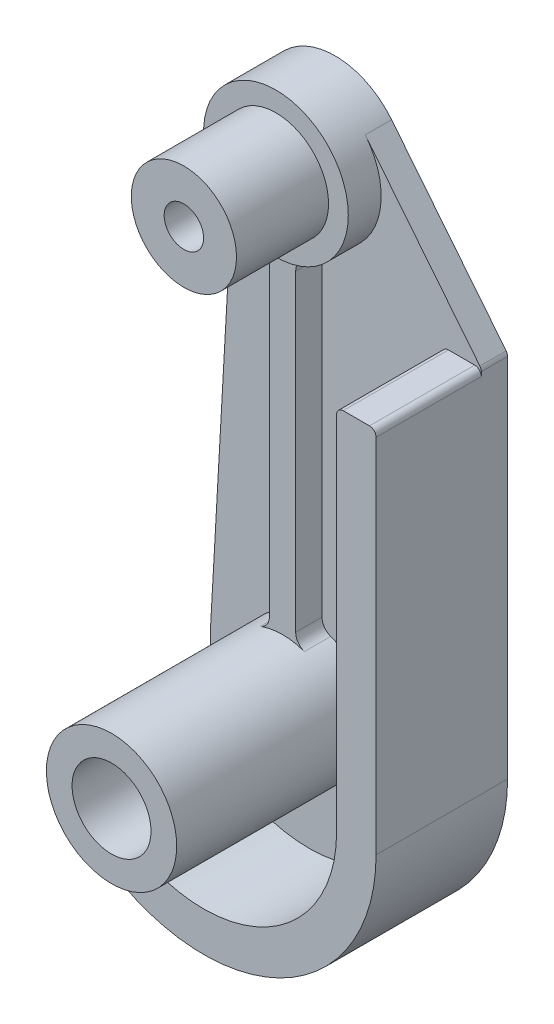
SolidWorks part; units mm, degrees
note: The reader was unsure of these and kept them because the rebuilt part matched: shared geometry of "Sketch1<3>", "Sketch1<5>", "Sketch1<6>", "Sketch1<7>".
ref_plane "Front Plane" through (0, 0, 0) normal (0, 0, 1) x (1, 0, 0)
ref_plane "Top Plane" through (0, 0, 0) normal (0, 1, 0) x (1, 0, 0)
ref_plane "Right Plane" through (0, 0, 0) normal (1, 0, 0) x (0, 0, -1)
sketch "Sketch1" plane through (0, 0, 0) normal (0, 0, 1) x (1, 0, 0)
  line L0 (0, 0) -> (0, 35.56) construction
  line L2 (13.1124, 0) -> (13.1124, 28)
  line L3 (0, 0) -> (0, 35.56) construction
  line L5 (10.1124, 0) -> (10.1124, 28)
  line L6 (10.1124, 0) -> (0, 0) construction
  line L7 (10.1124, 0) -> (13.1124, 0)
  line L8 (10.1124, 28) -> (13.1124, 28)
  line L9 (-7.4881, 0.4218) -> (-5.4913, 35.8693)
  line L10 (-5.0562, -8.7576) -> (-6.5562, -11.3556)
  line L11 (-5.0562, -8.7576) -> (0, 0) construction
  line L12 (-5.0562, -8.7576) -> (-3.75, -6.4952)
  line L13 (4.2908, 39.0008) -> (13.1124, 28)
  circle A0 centre (0, 0) radius 4.953
  circle A1 centre (0, 0) radius 3
  arc A2 (-6.5562, -11.3556) -> (13.1124, 0) centre (0, 0) ccw
  arc A4 (-5.0562, -8.7576) -> (10.1124, 0) centre (0, 0) ccw
  circle A6 centre (0, 35.56) radius 1.5
  circle A7 centre (0, 35.56) radius 5.5
  arc A8 (-7.4881, 0.4218) -> (-3.75, -6.4952) centre (0, 0) ccw
  circle A9 centre (0, 35.56) radius 4
  dimension "D1" = 6
  dimension "D2" = 9.906
  dimension "D5" = 20.2248
  dimension "D6" = 3
  dimension "D8" = 3
  dimension "D9" = 11
  dimension "D12" = 150
  dimension "D13" = 7.5
  dimension "D4" = 8
  dimension "D11" = 28
  dimension "D14" = 35.56
extrude "Boss-Extrude1" add sketch "Sketch1" along normal blind 2 contours A7 A6 | L9 A8 L12 A4 L5 L8 L13 A7 A0 | A0 A1 | L8 L5 L7 L2 | A4 L10 A2 L7
extrude "Boss-Extrude2" add sketch "Sketch1<3>" along normal blind 17 contours A0 A1
sketch "Sketch1<3>" plane through (0, 0, 0) normal (0, 0, 1) x (1, 0, 0) same geometry as "Sketch1"
extrude "Boss-Extrude3" add sketch "Sketch1<5>" along normal blind 10 contours L8 L5 L7 L2
sketch "Sketch1<5>" plane through (0, 0, 0) normal (0, 0, 1) x (1, 0, 0) same geometry as "Sketch1"
extrude "Boss-Extrude4" add sketch "Sketch1<6>" along normal blind 11.5 contours A9 A6
sketch "Sketch1<6>" plane through (0, 0, 0) normal (0, 0, 1) x (1, 0, 0) same geometry as "Sketch1"
extrude "Boss-Extrude5" add sketch "Sketch1<7>" along normal blind 2.5 from surface at 2 contours A7 A9 starting at face at (4, 35.56, 2)
sketch "Sketch1<7>" plane through (0, 0, 0) normal (0, 0, 1) x (1, 0, 0) same geometry as "Sketch1"
sketch "Sketch3" plane through (0, 0, 2) normal (0, 0, 1) x (1, 0, 0)
  line L1 (-1, 30.1517) -> (1, 30.1517)
  line L2 (-1, 30.1517) -> (-1, 4.851)
  line L3 (-1, 4.851) -> (1, 4.851)
  line L4 (1, 30.1517) -> (1, 4.851)
  circle A0 centre (0, 0) radius 4.953 construction
  circle A1 centre (0, 0) radius 4.953 construction
  arc A2 (-5.4913, 35.8693) -> (4.2908, 39.0008) centre (0, 35.56) ccw construction
  point P4 (1.1663, 4.8137)
  point P7 (-0.978, 4.8555)
  point P10 (-1, 30.1517)
  dimension "D1" = 2
extrude "Boss-Extrude6" add sketch "Sketch3" along normal blind 2
fillet "Fillet3" radius 0.5 2 edges at (13.1124, 28, 6) (10.1124, 28, 6)
fillet "Fillet4" radius 0.5 1 edges at (13.1124, 28, 1)
fillet "Fillet5" radius 0.5 3 edges at (-6.5562, -11.3556, 5) (-5.0562, -8.7576, 6) (-3.75, -6.4952, 1)
fillet "Fillet6" radius 1 4 edges at (1, 30.1517, 3) (-1, 30.1517, 3) (1, 4.851, 3) (-1, 4.851, 3)
